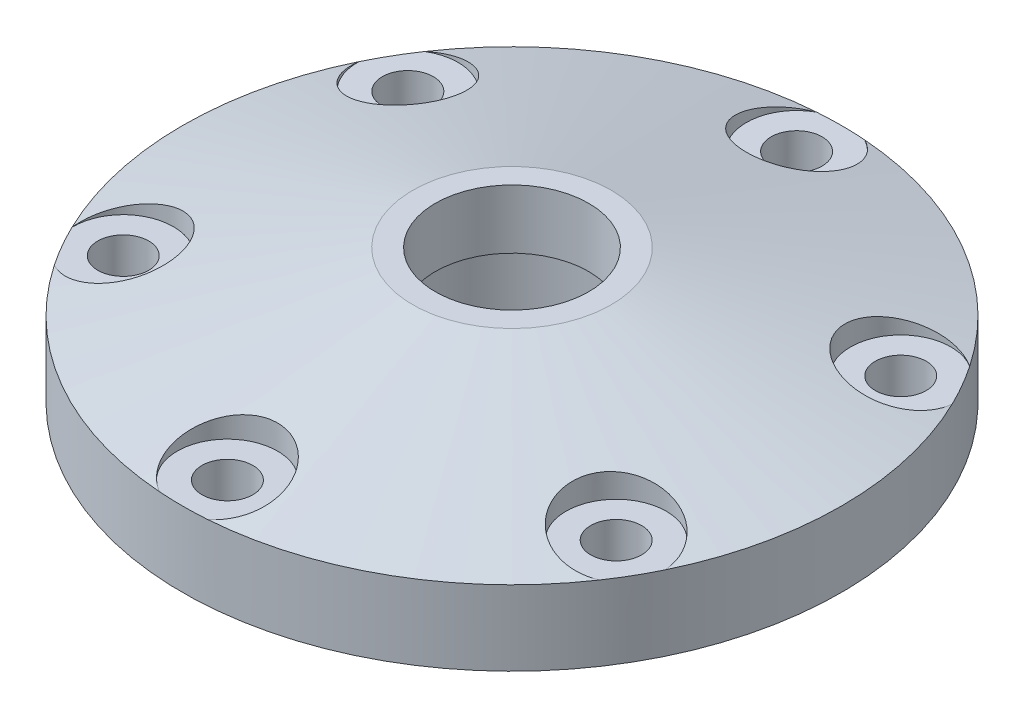
SolidWorks part; units mm, degrees
material "Nylon 6/10"
ref_plane "Front Plane" through (0, 0, 0) normal (0, 0, 1) x (1, 0, 0)
ref_plane "Top Plane" through (0, 0, 0) normal (0, 1, 0) x (1, 0, 0)
ref_plane "Right Plane" through (0, 0, 0) normal (1, 0, 0) x (0, 0, -1)
sketch "Sketch1" plane through (0, 0, 0) normal (0, 0, 1) x (1, 0, 0)
  line L0 (0, 0) -> (0, 11.9562) construction
  line L1 (5.12, 5) -> (5.12, 8.9453)
  line L2 (5.12, 8.9453) -> (6.625, 8.9453)
  line L3 (6.625, 8.9453) -> (22, 5)
  line L6 (22, 5) -> (22, 0)
  line L7 (22, 0) -> (6.75, 0)
  line L8 (5.12, 5) -> (6.75, 5)
  line L9 (6.75, 5) -> (6.75, 0)
  point P2 (22.1355, 7.5673)
  dimension "D1" = 10.24
  dimension "D2" = 5
  dimension "D3" = 13.5
  dimension "D5" = 13.25
  dimension "D7" = 8.9453
  dimension "D8" = 5
  dimension "D9" = 44
revolve "Revolve1" add sketch "Sketch1" angle 360 about L0
ref_plane "Plane1" through (0, 5, 0) normal (0, 1, 0) x (1, 0, 0)
sketch "Sketch2" plane through (0, 5, 0) normal (0, 1, 0) x (1, 0, 0)
  point P0 (0, 19)
  point P4 (16.4545, 9.5)
  point P5 (16.4545, -9.5)
  point P6 (0, -19)
  point P7 (-16.4545, -9.5)
  point P8 (-16.4545, 9.5)
  point P9 (0, 0)
  dimension "D2" = 38
  dimension "D1" = 6
hole_wizard "M3 Clearance Hole1" positions "Sketch2" profile "Sketch3" hole size "M3" standard "ANSI Metric"
sketch "Sketch3" plane through (0, 5, -19) normal (1, 0, 0) x (0, 0, 1)
  line L0 (0, 0) -> (0, 6.0215)
  line L1 (0, 6.0215) -> (1.7, 5)
  line L2 (1.7, 5) -> (1.7, 0)
  line L5 (1.7, 0) -> (0, 0)
  line L10 (0, 6.0215) -> (-1.7, 5) construction
  line L11 (0, -6.35) -> (0, 107.95) construction
  dimension "Hole Dia." = 3.4
  dimension "Hole Depth" = 5
  dimension "Drill Angle" = 118
sketch "Sketch4" plane through (0, 5, 0) normal (0, 1, 0) x (1, 0, 0)
  circle A0 centre (-16.4545, 9.5) radius 1.7 construction
  circle A1 centre (0, 19) radius 1.7 construction
  circle A2 centre (16.4545, 9.5) radius 1.7 construction
  circle A3 centre (16.4545, -9.5) radius 1.7 construction
  circle A4 centre (0, -19) radius 1.7 construction
  circle A5 centre (-16.4545, -9.5) radius 1.7 construction
  circle A6 centre (-16.4545, 9.5) radius 1.7
  circle A7 centre (0, 19) radius 1.7
  circle A8 centre (16.4545, 9.5) radius 1.7
  circle A9 centre (16.4545, -9.5) radius 1.7
  circle A10 centre (0, -19) radius 1.7
  circle A11 centre (-16.4545, -9.5) radius 1.7
  point P0 (-16.4545, 9.5)
  point P2 (0, 19)
  point P4 (16.4545, 9.5)
  point P6 (16.4545, -9.5)
  point P8 (0, -19)
  point P10 (-16.4545, -9.5)
hole_wizard "CBORE for M3 SBHCS7" positions "Sketch4" profile "Sketch5" counterbore size "M3" standard "ANSI Metric"
sketch "Sketch5" plane through (-16.4545, 5, -9.5) normal (1, 0, 0) x (0, 0, -1)
  line L0 (0, 0) -> (0, 4.9668)
  line L1 (0, 4.9668) -> (1.7, 3.9453)
  line L2 (1.7, 3.9453) -> (1.7, 1.65)
  line L3 (1.7, 1.65) -> (3.35, 1.65)
  line L4 (3.35, 1.65) -> (3.35, 0)
  line L5 (3.35, 0) -> (0, 0)
  line L10 (0, 4.9668) -> (-1.7, 3.9453) construction
  line L11 (0, -6.35) -> (0, 107.95) construction
  dimension "Hole Dia." = 3.4
  dimension "Hole Depth" = 3.9453
  dimension "C'Bore Dia." = 6.7
  dimension "C'Bore Depth" = 1.65
  dimension "Drill Angle" = 118
